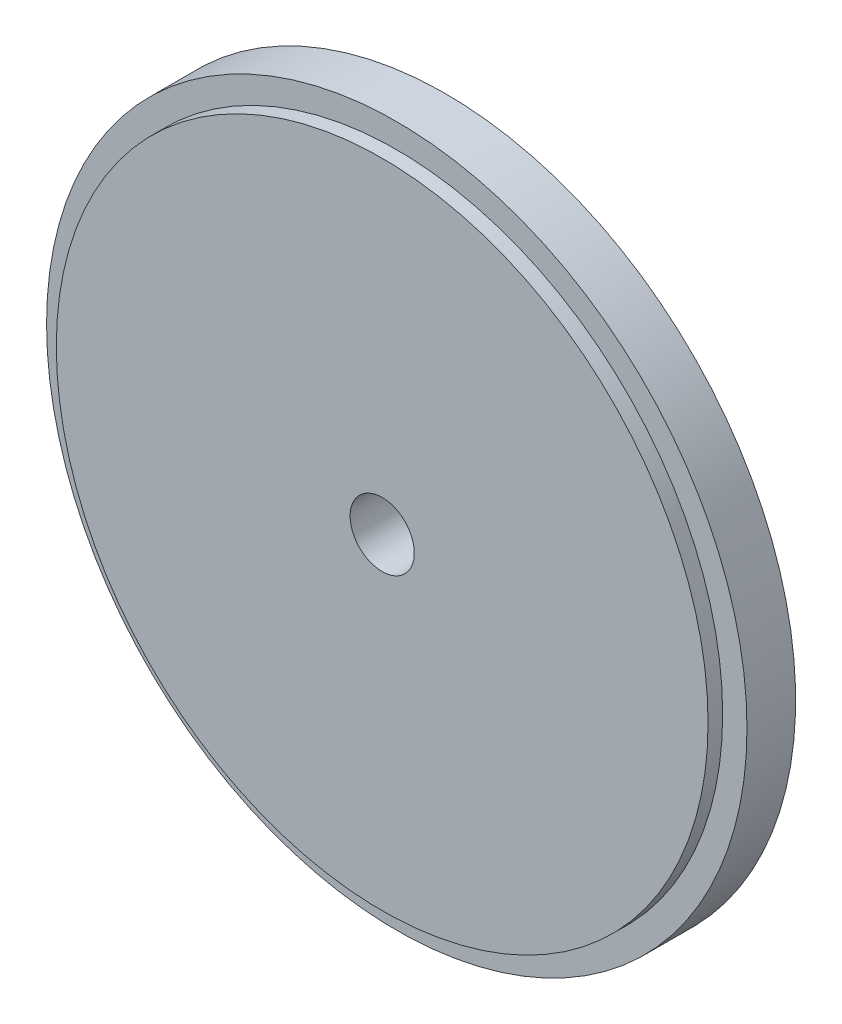
SolidWorks part; units mm, degrees
material "Liga 1060"
ref_plane "Plano frontal" through (0, 0, 0) normal (0, 0, 1) x (1, 0, 0)
ref_plane "Plano superior" through (0, 0, 0) normal (0, 1, 0) x (1, 0, 0)
ref_plane "Plano direito" through (0, 0, 0) normal (1, 0, 0) x (0, 0, -1)
sketch "Esboço1" plane through (0, 0, 0) normal (0, 0, 1) x (1, 0, 0)
  circle A0 centre (0, 0) radius 32.5
  circle A1 centre (0, 0) radius 35
extrude "Ressalto-extrusão1" add sketch "Esboço1" along normal blind 8
sketch "Esboço2" plane through (0, 0, 8) normal (0, 0, 1) x (1, 0, 0)
  circle A0 centre (0, 0) radius 32.5
extrude "Ressalto-extrusão2" add sketch "Esboço2" against normal blind 3
sketch "Esboço3" plane through (0, 0, 8) normal (0, 0, 1) x (1, 0, 0)
  circle A0 centre (0, 0) radius 2.5
extrude "Corte-extrusão1" cut sketch "Esboço3" against normal blind 3
sketch "Esboço4" plane through (0, 0, 5) normal (0, 0, -1) x (-1, 0, 0)
  circle A0 centre (0, 0) radius 37
  circle A1 centre (0, 0) radius 35
extrude "Ressalto-extrusão3" add sketch "Esboço4" against normal through all and the other way through all
sketch "Esboço5" plane through (0, 0, 0) normal (0, 1, 0) x (1, 0, 0)
  line L0 (-37, -1) -> (-37, -7)
  line L1 (-37, -4) -> (-13.2615, -4)
  line L2 (-35.2, -4) -> (-35.2, -1)
  line L3 (-35.2, -1) -> (-37, -1)
  line L4 (-35.2, -4) -> (-35.2, -7)
  line L5 (-35.2, -7) -> (-37, -7)
revolve "Corte-Revolução1" cut sketch "Esboço5" angle 360 about axis through (0, 0, 8) along (0, 0, -1) region at (-36.1, 0, 2.5) region at (-36.1, 0, 5.5)
sketch "Esboço6" plane through (0, 0, 5) normal (0, 0, -1) x (-1, 0, 0)
  circle A0 centre (0, 0) radius 12.55
  dimension "D1" = 25.1
extrude "Ressalto-extrusão4" add sketch "Esboço6" along normal blind 5
sketch "Esboço7" plane through (0, 0, 0) normal (0, 0, -1) x (-1, 0, 0)
  circle A0 centre (0, 0) radius 7.55
  dimension "D1" = 15.1
extrude "Corte-extrusão2" cut sketch "Esboço7" against normal through all both and the other way through all
sketch "Esboço8" plane through (0, 0, 8) normal (0, 0, 1) x (1, 0, 0)
  circle A0 centre (0, 0) radius 37
  circle A1 centre (0, 0) radius 32.5
  dimension "D1" = 74
extrude "Ressalto-extrusão5" add sketch "Esboço8" against normal up to surface (8 mm away) up to face at (32.5, 0, 0)
sketch "Esboço9" plane through (0, 0, 8) normal (0, 0, 1) x (1, 0, 0)
  circle A0 centre (0, 0) radius 37
  circle A1 centre (0, 0) radius 33.5
extrude "Corte-extrusão8" cut sketch "Esboço9" against normal blind 1.5
sketch "Esboço12" plane through (0, 0, 0) normal (0, 0, -1) x (-1, 0, 0)
  circle A0 centre (0, 0) radius 37
  circle A1 centre (0, 0) radius 33.5
  dimension "D1" = 74
extrude "Corte-extrusão9" cut sketch "Esboço12" against normal blind 1.5
sketch "Esboço13" plane through (0, 0, 1.5) normal (0, 0, -1) x (-1, 0, 0)
  circle A1 centre (0, 0) radius 36
  circle A2 centre (0, 0) radius 37
extrude "Corte-extrusão10" cut sketch "Esboço13" against normal blind 10
sketch "Esboço14" plane through (0, 0, 6.5) normal (0, 0, 1) x (1, 0, 0)
  circle A0 centre (0, 0) radius 37
  circle A1 centre (0, 0) radius 36
  circle A3 centre (0, 0) radius 36
  circle A6 centre (0, 0) radius 36
  circle M3 centre (0, 0) radius 36
  dimension "D1" = 0
extrude "Ressalto-extrusão6" add sketch "Esboço14" against normal up to surface (5 mm away) contours A0 M3 region at (-36.8953, 0, 6.5) up to face at (-33.5, 0, 1.5)
sketch "Esboço15" plane through (0, 0, 0) normal (0, 0, -1) x (-1, 0, 0)
  circle A0 centre (0, 0) radius 12.55
extrude "Corte-extrusão11" cut sketch "Esboço15" against normal through all
sketch "Esboço16" plane through (0, 0, 5) normal (0, 0, -1) x (-1, 0, 0)
  circle A0 centre (0, 0) radius 12.55 construction
  circle A1 centre (0, 0) radius 12.55
extrude "Ressalto-extrusão7" add sketch "Esboço16" against normal through all
sketch "Esboço17" plane through (0, 0, 5) normal (0, 0, -1) x (-1, 0, 0)
  circle A0 centre (0, 0) radius 10
  dimension "D1" = 20
extrude "Ressalto-extrusão8" add sketch "Esboço17" along normal blind 16
sketch "Esboço18" plane through (0, 0, -11) normal (0, 0, -1) x (-1, 0, 0)
  circle A0 centre (0, 0) radius 3.3
  dimension "D1" = 6.6
extrude "Corte-extrusão12" cut sketch "Esboço18" against normal blind 16
sketch "Esboço19" plane through (0, 0, -11) normal (0, 0, -1) x (-1, 0, 0)
  line L0 (0, -3.3) -> (0, -5.3) construction
  line L1 (-2.975, -5.3) -> (2.975, -5.3)
  line L2 (2.975, -5.3) -> (2.975, -7.95)
  line L3 (2.975, -7.95) -> (-2.975, -7.95)
  line L4 (-2.975, -7.95) -> (-2.975, -5.3)
  line L5 (-3.3, 0) -> (3.3, 0) construction
  line L6 (-2.975, 7.95) -> (-2.975, 5.3)
  line L7 (2.975, 7.95) -> (-2.975, 7.95)
  line L8 (2.975, 5.3) -> (2.975, 7.95)
  line L9 (-2.975, 5.3) -> (2.975, 5.3)
  circle A1 centre (0, 0) radius 3.3 construction
  circle A2 centre (0, 0) radius 3.3 construction
  point P12 (0, -5.3)
  point P19 (0, 5.3)
  dimension "D1" = 2
  dimension "D2" = 5.95
  dimension "D3" = 2.65
extrude "Corte-extrusão13" cut sketch "Esboço19" against normal blind 8
sketch "Esboço21" plane through (0, 5.3, 0) normal (0, 1, 0) x (1, 0, 0)
  line L0 (0, 11) -> (0, 8.5) construction
  line L1 (-2.975, 11) -> (2.975, 11) construction
  circle A0 centre (0, 6.85) radius 1.65
  dimension "D2" = 3.3
  dimension "D1" = 2.5
extrude "Corte-extrusão14" cut sketch "Esboço21" against normal through all both and the other way through all
sketch "Esboço23" plane through (0, 0, 1.5) normal (0, 0, -1) x (-1, 0, 0)
  circle A0 centre (0, 0) radius 36
  circle A1 centre (0, 0) radius 37 construction
  circle A2 centre (0, 0) radius 37
  dimension "D1" = 72
extrude "Corte-extrusão15" cut sketch "Esboço23" against normal through all
sketch "Esboço24" plane through (0, 0, -11) normal (0, 0, -1) x (-1, 0, 0)
  circle A0 centre (0, 0) radius 3.3
extrude "Corte-extrusão16" cut sketch "Esboço24" against normal through all
